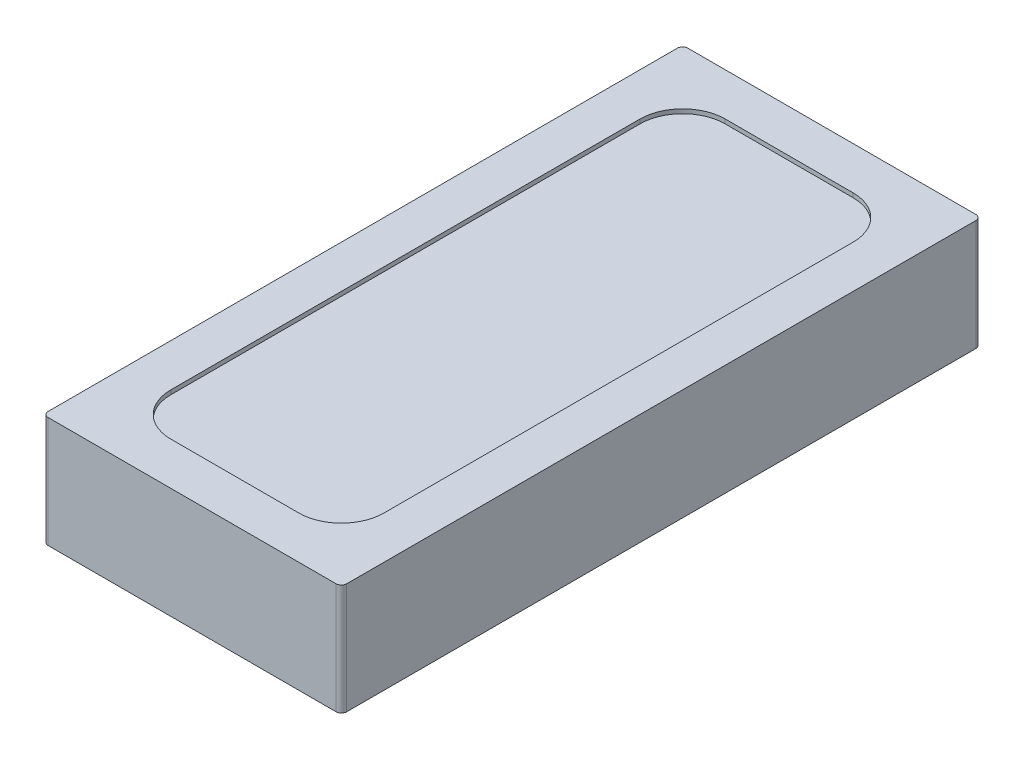
SolidWorks part; units mm, degrees
ref_plane "Front Plane" through (0, 0, 0) normal (0, 0, 1) x (1, 0, 0)
ref_plane "Top Plane" through (0, 0, 0) normal (0, 1, 0) x (1, 0, 0)
ref_plane "Right Plane" through (0, 0, 0) normal (1, 0, 0) x (0, 0, -1)
sketch "Sketch1" plane through (0, 0, 0) normal (0, 1, 0) x (1, 0, 0)
  line L1 (-0.675, -1.5) -> (0.675, -1.5)
  line L2 (-0.7, -1.475) -> (-0.7, 1.475)
  line L3 (-0.675, 1.5) -> (0.675, 1.5)
  line L4 (0.7, -1.475) -> (0.7, 1.475)
  line L5 (-0.7, -1.5) -> (0.7, 1.5) construction
  line L6 (-0.7, 1.5) -> (0.7, -1.5) construction
  arc A0 (-0.7, 1.475) -> (-0.675, 1.5) centre (-0.675, 1.475) cw
  arc A1 (0.675, 1.5) -> (0.7, 1.475) centre (0.675, 1.475) cw
  arc A2 (0.675, -1.5) -> (0.7, -1.475) centre (0.675, -1.475) ccw
  arc A3 (-0.675, -1.5) -> (-0.7, -1.475) centre (-0.675, -1.475) cw
  point P0 (0, 0)
  dimension "D3" = 0.025
  dimension "D1" = 1.4
  dimension "D2" = 3
extrude "Boss-Extrude1" add sketch "Sketch1" along normal blind 0.52
sketch "Sketch2" plane through (0, 0.52, 0) normal (0, 1, 0) x (1, 0, 0)
  line L1 (-0.3, -1.3) -> (0.3, -1.3)
  line L2 (-0.5, -1.1) -> (-0.5, 1.1)
  line L3 (-0.3, 1.3) -> (0.3, 1.3)
  line L4 (0.5, -1.1) -> (0.5, 1.1)
  line L5 (-0.5, -1.3) -> (0.5, 1.3) construction
  line L6 (-0.5, 1.3) -> (0.5, -1.3) construction
  arc A0 (0.3, -1.3) -> (0.5, -1.1) centre (0.3, -1.1) ccw
  arc A1 (0.3, 1.3) -> (0.5, 1.1) centre (0.3, 1.1) cw
  arc A2 (-0.5, 1.1) -> (-0.3, 1.3) centre (-0.3, 1.1) cw
  arc A3 (-0.3, -1.3) -> (-0.5, -1.1) centre (-0.3, -1.1) cw
  point P0 (0, 0)
  dimension "D3" = 0.2
  dimension "D1" = 2.6
  dimension "D2" = 1
extrude "Cut-Extrude1" cut sketch "Sketch2" against normal blind 0.02
